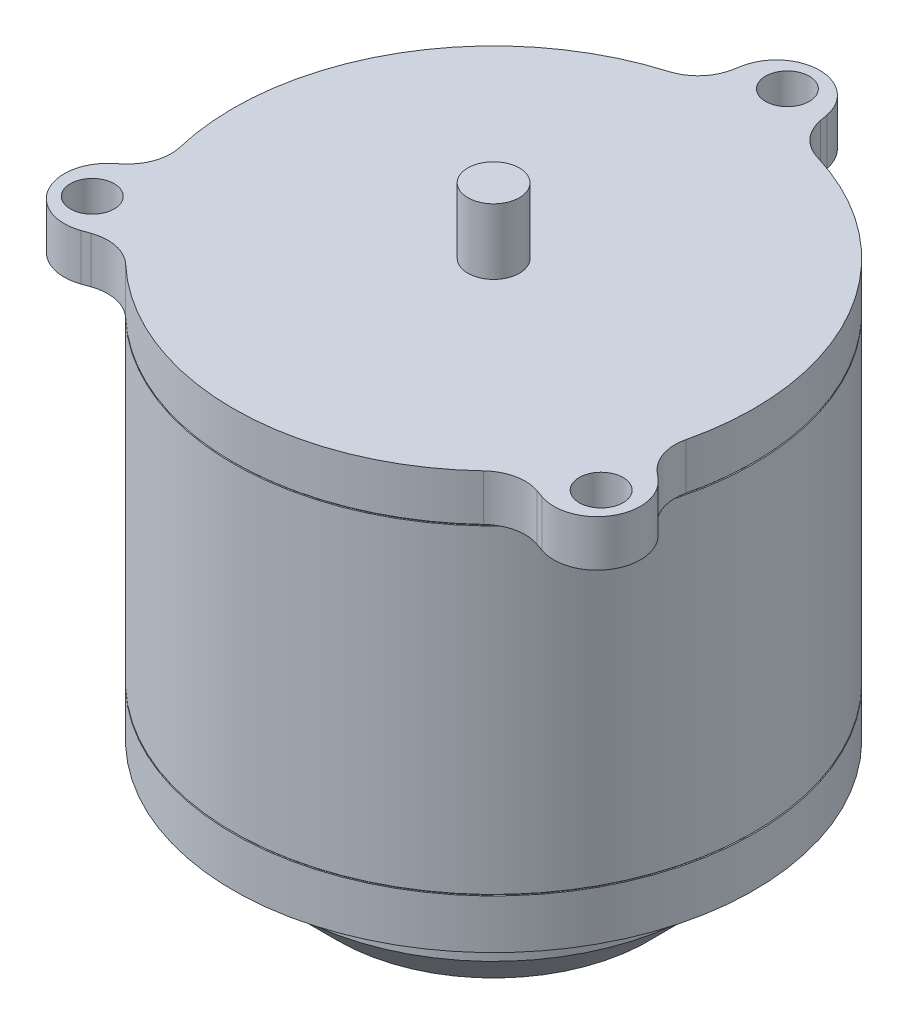
SolidWorks part; units mm, degrees
ref_plane "Front Plane" through (0, 0, 0) normal (0, 0, 1) x (1, 0, 0)
ref_plane "Top Plane" through (0, 0, 0) normal (0, 1, 0) x (1, 0, 0)
ref_plane "Right Plane" through (0, 0, 0) normal (1, 0, 0) x (0, 0, -1)
sketch "Sketch1" plane through (0, 0, 0) normal (0, 0, 1) x (1, 0, 0)
  line L0 (0, 78.6404) -> (0, -19.8873)
  line L1 (0, -19.8873) -> (16, -19.8873)
  line L2 (16, -19.8873) -> (16, -11.9498)
  line L3 (16, -11.9498) -> (30.1625, -11.9498)
  line L4 (30.1625, -11.9498) -> (39.6875, -2.4248)
  line L5 (39.6875, -2.4248) -> (39.6875, 6.6949)
  line L6 (39.6875, 6.6949) -> (50.5, 6.6949)
  line L7 (50.5, 6.6949) -> (50.5, 16.2199)
  line L8 (50.5, 16.2199) -> (50.246, 16.2199)
  line L9 (50.246, 16.2199) -> (50.246, 16.4739)
  line L10 (50.246, 16.4739) -> (50.5, 16.4739)
  line L11 (50.5, 16.4739) -> (50.5, 78.3864)
  line L12 (50.5, 78.3864) -> (50.246, 78.3864)
  line L13 (50.246, 78.3864) -> (50.246, 78.6404)
  line L15 (50.246, 78.6404) -> (0, 78.6404)
  line L16 (0, -28.5299) -> (0, 93.8546) construction
  dimension "D1" = 7.9375
  dimension "D2" = 32
  dimension "D3" = 79.375
  dimension "D4" = 45
  dimension "D5" = 0.254
  dimension "D6" = 0.254
  dimension "D7" = 9.1197
  dimension "D8" = 101
  dimension "D9" = 0.254
  dimension "D10" = 9.525
  dimension "D11" = 61.9125
  dimension "D12" = 9.525
revolve "Revolve1" add sketch "Sketch1" angle 360 about L16
sketch "Sketch3" plane through (0, 78.6404, 0) normal (0, 1, 0) x (1, 0, 0)
  line L0 (0, 0) -> (0, 50.5) construction
  line L1 (0, 0) -> (-43.7343, -25.25) construction
  line L2 (0, 0) -> (43.7343, -25.25) construction
  line L3 (-8.2463, 56.4003) -> (-8.5278, 54.902)
  line L4 (8.5278, 54.902) -> (8.2463, 56.4003)
  line L5 (0, 50.5) -> (0, 100.2976) construction
  arc A0 (-14.3842, 48.4081) -> (14.3842, 48.4081) centre (0, 0) ccw
  circle A1 centre (0, 0) radius 50.5 construction
  arc A2 (-8.2463, 56.4003) -> (8.2463, 56.4003) centre (0, 54.8512) cw
  arc A3 (8.5278, 54.902) -> (14.3842, 48.4081) centre (16.7741, 56.4511) ccw
  arc A4 (-8.5278, 54.902) -> (-14.3842, 48.4081) centre (-16.7741, 56.4511) cw
  circle A5 centre (0, 57) radius 4.25
  circle A6 centre (0, 0) radius 57 construction
  point P16 (9.525, 49.5936)
  point P19 (-9.525, 49.5936)
  dimension "D7" = 114
  dimension "D5" = 8.5
  dimension "D1" = 120
  dimension "D2" = 120
  dimension "D3" = 9.525
  dimension "D4" = 9.525
extrude "Boss-Extrude1" add sketch "Sketch3" along normal blind 9
pattern_circular "CirPattern1" count 3 over 360 about axis through (0, 87.6404, 0) along (0, -1, 0) of "Boss-Extrude1"
sketch "Sketch4" plane through (0, 87.6404, 0) normal (0, 1, 0) x (1, 0, 0)
  circle A0 centre (0, 0) radius 5
  dimension "D1" = 10
extrude "Boss-Extrude2" add sketch "Sketch4" along normal blind 12.7
ref_axis "Axis1" through (0, 71.469, 0) along (0, -1, 0)
